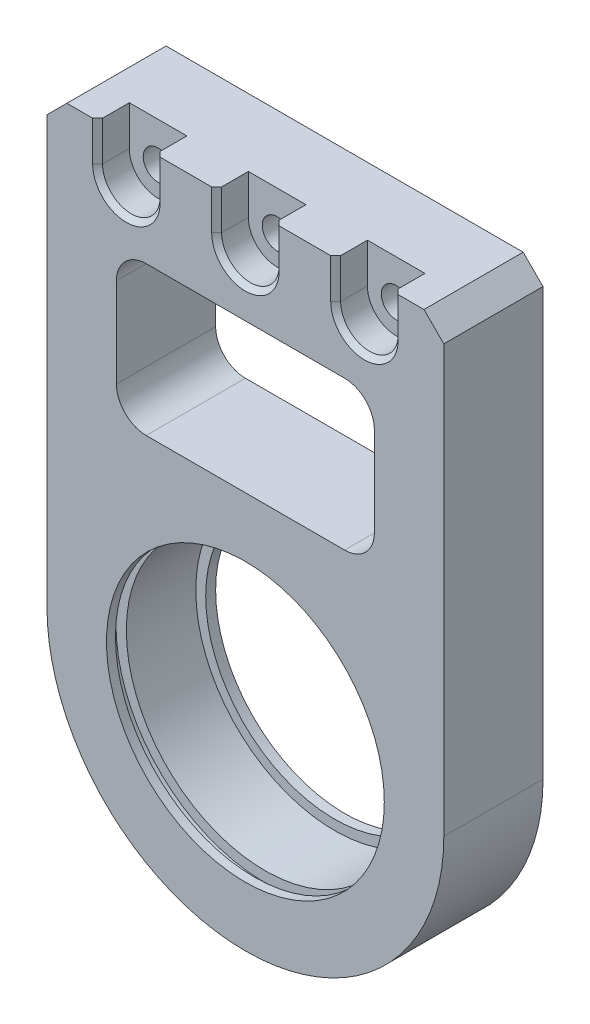
SolidWorks part; units mm, degrees
ref_plane "前视基准面" through (0, 0, 0) normal (0, 0, 1) x (1, 0, 0)
ref_plane "上视基准面" through (0, 0, 0) normal (0, 1, 0) x (1, 0, 0)
ref_plane "右视基准面" through (0, 0, 0) normal (1, 0, 0) x (0, 0, -1)
other "Configuration Table"
sketch "草图1" plane through (0, 0, 0) normal (0, 0, 1) x (1, 0, 0)
  line L1 (0, -5) -> (40, -5)
  line L2 (0, -5) -> (0, -70)
  line L3 (0, -70) -> (40, -70)
  line L4 (40, -5) -> (40, -70)
  dimension "D1" = 40
  dimension "D2" = 65
extrude "凸台-拉伸1" add sketch "草图1" along normal blind 10
sketch "草图2" plane through (0, 0, 10) normal (0, 0, 1) x (1, 0, 0)
  line L0 (0, -70) -> (40, -70) construction
  line L2 (0, -5) -> (0, -70) construction
  circle A0 centre (20, -50) radius 14
  dimension "D1" = 28
  dimension "D2" = 20
  dimension "D3" = 20
extrude "切除-拉伸1" cut sketch "草图2" against normal blind 12
ref_plane "基准面1" through (0, 0, 8) normal (0, 0, -1) x (-1, 0, 0)
sketch "草图3" plane through (0, 0, 8) normal (0, 0, -1) x (-1, 0, 0)
  circle A0 centre (-20, -50) radius 15.05
  dimension "D1" = 30.1
extrude "切除-拉伸2" cut sketch "草图3" against normal blind 1.1
chamfer "倒角1" distance 2 angle 45 2 edges at (40, -5, 5) (0, -5, 5)
fillet "圆角1" radius 20 2 edges at (0, -70, 5) (40, -70, 5)
sketch "草图4" plane through (0, 0, 0) normal (0, 0, -1) x (-1, 0, 0)
  line L0 (-40, -50) -> (-40, -7) construction
  line L1 (-38, -5) -> (-2, -5) construction
  circle A0 centre (-32, -9) radius 1.5
  circle A1 centre (-20, -9) radius 1.5
  circle A2 centre (-8, -9) radius 1.5
  dimension "D1" = 3
  dimension "D2" = 8
  dimension "D3" = 4
  dimension "D4" = 2
  dimension "D5" = 2
extrude "切除-拉伸3" cut sketch "草图4" against normal blind 15
sketch "草图5" plane through (0, 0, 0) normal (0, 0, -1) x (-1, 0, 0)
  line L0 (-40, -50) -> (-40, -7) construction
  line L1 (-33, -15) -> (-7, -15)
  line L2 (-33, -15) -> (-33, -30)
  line L3 (-33, -30) -> (-7, -30)
  line L4 (-7, -15) -> (-7, -30)
  line L5 (-33, -15) -> (-7, -30) construction
  line L6 (-33, -30) -> (-7, -15) construction
  line L7 (-38, -5) -> (-2, -5) construction
  point P0 (-20, -22.5)
  dimension "D1" = 26
  dimension "D2" = 15
  dimension "D3" = 7
  dimension "D4" = 10
extrude "切除-拉伸4" cut sketch "草图5" against normal blind 15
fillet "圆角2" radius 3 4 edges at (7, -30, 5) (7, -15, 5) (33, -30, 5) (33, -15, 5)
sketch "草图7" plane through (0, 0, 0) normal (0, 0, -1) x (-1, 0, 0)
  circle A0 centre (-20, -50) radius 14
  circle A1 centre (-20, -50) radius 14 construction
  circle A2 centre (-20, -50) radius 13
  dimension "D1" = 28
  dimension "D2" = 0
  dimension "D3" = 26
extrude "凸台-拉伸2" add sketch "草图7" against normal blind 1
sketch "草图8" plane through (0, 0, 10) normal (0, 0, 1) x (1, 0, 0)
  line L0 (38, -5) -> (2, -5) construction
  line L2 (5.1, -9) -> (5.1, -5)
  line L3 (5.1, -5) -> (10.9, -5)
  line L4 (10.9, -9) -> (10.9, -5)
  line L5 (17.1, -9) -> (17.1, -5)
  line L6 (22.9, -9) -> (22.9, -5)
  line L7 (34.9, -9) -> (34.9, -5)
  line L8 (29.1, -5) -> (34.9, -5)
  line L9 (29.1, -9) -> (29.1, -5)
  line L10 (17.1, -5) -> (22.9, -5)
  arc A0 (5.1, -9) -> (10.9, -9) centre (8, -9) ccw
  arc A2 (17.1, -9) -> (22.9, -9) centre (20, -9) ccw
  arc A3 (29.1, -9) -> (34.9, -9) centre (32, -9) ccw
  dimension "D1" = 5.8
  dimension "D2" = 5.8
  dimension "D3" = 2
  dimension "D4" = 2
extrude "切除-拉伸5" cut sketch "草图8" against normal blind 3.2
chamfer "倒角2" distance 0.5 angle 45 9 edges at (34.9, -7, 10) (32, -11.9, 10) (29.1, -7, 10) (22.9, -7, 10) (20, -11.9, 10) (17.1, -7, 10) (10.9, -7, 10) (8, -11.9, 10) (5.1, -7, 10)
